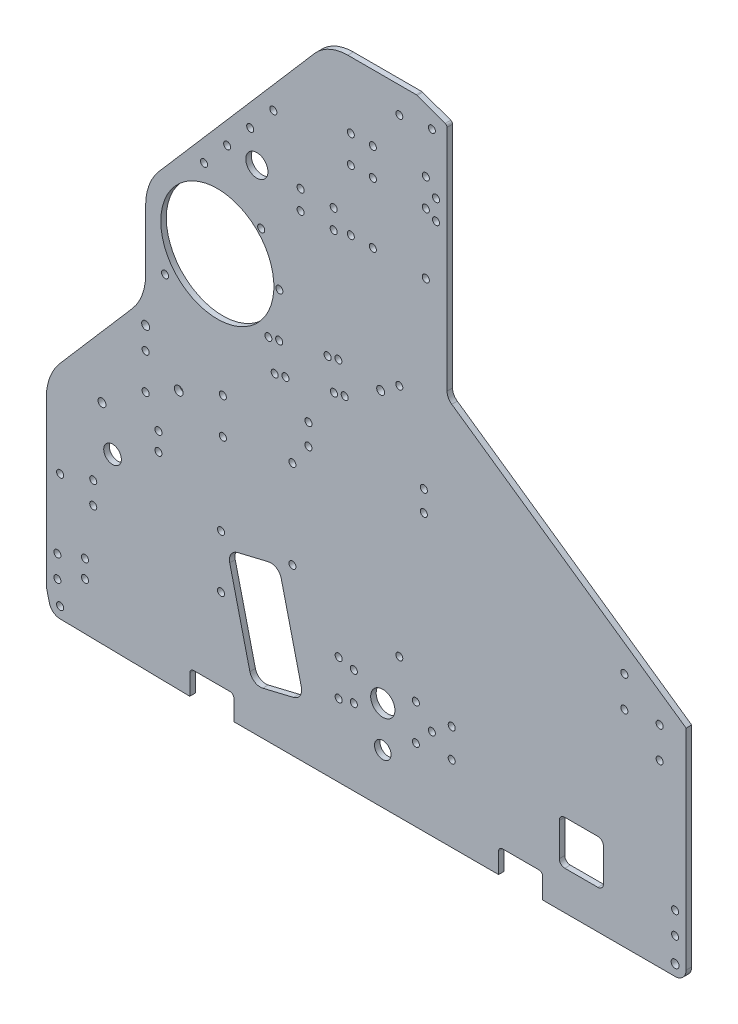
SolidWorks part; units mm, degrees
ref_plane "Front Plane" through (0, 0, 0) normal (0, 0, 1) x (1, 0, 0)
ref_plane "Top Plane" through (0, 0, 0) normal (0, 1, 0) x (1, 0, 0)
ref_plane "Right Plane" through (0, 0, 0) normal (1, 0, 0) x (0, 0, -1)
sketch "Sketch1" plane through (0, 0, 0) normal (0, 0, 1) x (1, 0, 0)
  line L0 (82.55, -20.32) -> (82.55, -6.35)
  line L2 (0, 0) -> (0, 157.48)
  line L4 (368.3, -20.32) -> (368.3, 106.68)
  line L5 (82.55, -6.35) -> (107.95, -6.35)
  line L6 (107.95, -6.35) -> (107.95, -20.32)
  line L7 (107.95, -20.32) -> (260.35, -20.32)
  line L8 (260.35, -20.32) -> (260.35, -6.35)
  line L9 (260.35, -6.35) -> (285.75, -6.35)
  line L10 (285.75, -6.35) -> (285.75, -20.32)
  line L11 (285.75, -20.32) -> (368.3, -20.32)
  line L12 (361.95, 12.7) -> (368.3, 12.7) construction
  line L13 (0, 0) -> (6.35, 0) construction
  line L14 (0.1896, -7.8901) -> (1.7771, -14.2401)
  line L15 (7.8295, -19.0491) -> (82.55, -20.32)
  line L16 (0, 0) -> (0, -6.35)
  line L17 (76.2, 128.905) -> (79.375, 128.905) construction
  line L18 (57.15, 118.5863) -> (101.6, 118.5862) construction
  line L19 (57.15, 118.5863) -> (57.15, 139.2238) construction
  line L20 (101.6, 118.5862) -> (101.6, 139.2237) construction
  line L21 (57.15, 139.2238) -> (101.6, 139.2237) construction
  line L22 (57.15, 118.5863) -> (101.6, 139.2237) construction
  line L23 (101.6, 118.5862) -> (57.15, 139.2238) construction
  line L25 (203.2, 59.805) -> (203.2, 194.805) construction
  line L26 (203.2, 194.805) -> (203.2, 329.805) construction
  line L27 (355.6, 332.105) -> (330.2, 332.105) construction
  line L28 (330.2, 332.105) -> (330.2, 217.805) construction
  line L29 (330.2, 217.805) -> (355.6, 217.805) construction
  line L30 (355.6, 217.805) -> (355.6, 332.105) construction
  line L31 (203.2, 344.805) -> (203.2, 194.805) construction
  line L32 (50.8, 332.105) -> (76.2, 332.105) construction
  line L33 (76.2, 332.105) -> (76.2, 217.805) construction
  line L34 (50.8, 217.805) -> (50.8, 332.105) construction
  line L35 (76.2, 217.805) -> (50.8, 217.805) construction
  line L36 (213.2, 344.805) -> (230.6638, 338.455)
  line L37 (203.2, 344.805) -> (161.925, 344.805)
  line L38 (203.2, 344.805) -> (213.2, 344.805)
  line L39 (348.5362, 344.805) -> (413.4623, 344.805)
  line L40 (348.5362, 344.805) -> (230.6638, 344.805) construction
  line L42 (161.925, 344.805) -> (0, 157.48)
  line L44 (230.6638, 338.455) -> (230.6638, 202.565)
  line L45 (230.6638, 202.565) -> (368.3, 106.68)
  line L46 (213.2, 344.805) -> (-141.0713, 344.805) construction
  circle A0 centre (6.35, 0) radius 2.032
  circle A1 centre (6.35, 12.7) radius 2.032
  circle A2 centre (361.95, 0) radius 2.032
  circle A3 centre (361.95, 12.7) radius 2.032
  arc A5 (1.7771, -14.2401) -> (7.8295, -19.0491) centre (7.9375, -12.7) ccw
  circle A6 centre (7.9375, -12.7) radius 2.032
  arc A7 (0, -6.35) -> (0.1896, -7.8901) centre (6.35, -6.35) ccw
  circle A8 centre (38.1, 78.105) radius 5.08
  circle A9 centre (76.2, 128.905) radius 2.54
  circle A10 centre (101.6, 118.5862) radius 2.032
  circle A11 centre (101.6, 139.2237) radius 2.032
  circle A12 centre (57.15, 139.2238) radius 2.032
  circle A13 centre (57.15, 118.5863) radius 2.032
  circle A15 centre (203.2, 59.805) radius 2
  circle A16 centre (203.2, 194.805) radius 2
  circle A17 centre (203.2, 329.805) radius 2
  circle A18 centre (63.5, 313.055) radius 2.032
  circle A20 centre (355.6, 332.105) radius 2.032
  circle A21 centre (330.2, 332.105) radius 2.032
  circle A22 centre (355.6, 217.805) radius 2.032
  circle A23 centre (330.2, 217.805) radius 2.032
  circle A24 centre (50.8, 332.105) radius 2.032
  circle A25 centre (76.2, 332.105) radius 2.032
  circle A26 centre (50.8, 217.805) radius 2.032
  circle A27 centre (76.2, 217.805) radius 2.032
  circle A28 centre (221.9319, 332.105) radius 2
  circle A29 centre (224.3138, 298.831) radius 2.032
  circle A30 centre (353.06, 100.7351) radius 2.032
  circle A31 centre (332.74, 115.9751) radius 2.032
  circle A32 centre (332.74, 98.1951) radius 2.032
  circle A33 centre (353.06, 82.9551) radius 2.032
  circle A34 centre (117.3562, 280.4276) radius 2.032
  circle A35 centre (104.0678, 265.0548) radius 2.032
  circle A36 centre (90.7795, 249.682) radius 2.032
  circle A38 centre (130.6445, 295.8004) radius 2.032
  circle A39 centre (68.326, 182.9237) radius 2.032
  circle A40 centre (224.3138, 287.401) radius 2.032
  point P82 (203.2, 344.805)
  point P83 (221.9319, 341.63)
  point P90 (368.3, 62.484)
  dimension "D6" = 4.064
  dimension "D10" = 6.35
  dimension "D11" = 4.064
  dimension "D17" = 38.1
  dimension "D27" = 4
  dimension "D31" = 4.064
  dimension "D32" = 41.275
  dimension "D36" = 4.064
  dimension "D47" = 39.624
  dimension "D48" = 4.064
  dimension "D25" = 5.08
  dimension "D26" = 4.064
  dimension "D52" = 4.064
  dimension "D65" = 4.064
  dimension "D69" = 10.16
  dimension "D2" = 127
  dimension "D3" = 13.97
  dimension "D4" = 25.4
  dimension "D5" = 152.4
  dimension "D7" = 12.7
  dimension "D8" = 6.35
  dimension "D9" = 20.32
  dimension "D12" = 12.7
  dimension "D13" = 1.5875
  dimension "D14" = 82.55
  dimension "D15" = 368.3
  dimension "D16" = 6.35
  dimension "D18" = 98.425
  dimension "D19" = 38.1
  dimension "D20" = 50.8
  dimension "D21" = 3.175
  dimension "D22" = 270
  dimension "D23" = 20.6375
  dimension "D24" = 44.45
  dimension "D28" = 135
  dimension "D29" = 12.7
  dimension "D30" = 15
  dimension "D33" = 63.5
  dimension "D34" = 27.4638
  dimension "D35" = 12.7
  dimension "D37" = 114.3
  dimension "D38" = 25.4
  dimension "D39" = 12.7
  dimension "D40" = 157.48
  dimension "D41" = 142.24
  dimension "D42" = 365.125
  dimension "D43" = 10
  dimension "D44" = 6.35
  dimension "D45" = 31.75
  dimension "D46" = 6.35
  dimension "D49" = 6.35
  dimension "D50" = 203.2
  dimension "D51" = 15.24
  dimension "D53" = 17.78
  dimension "D54" = 17.78
  dimension "D55" = 20.32
  dimension "D56" = 15.24
  dimension "D57" = 92.202
  dimension "D58" = 8.382
  dimension "D59" = 20.32
  dimension "D60" = 20.32
  dimension "D61" = 8.382
  dimension "D62" = 20.32
  dimension "D63" = 8.382
  dimension "D64" = 8.382
  dimension "D66" = 35.052
  dimension "D67" = 68.326
  dimension "D68" = 11.43
extrude "Boss-Extrude1" add sketch "Sketch1" along normal blind 3.175 contours L16 A7 L14 A5 L15 L2 A0 A1 A6 region at (171.4477, 119.565, 0)
fillet "Fillet1" radius 2.286 4 edges at (285.75, -6.35, 1.5875) (107.95, -6.35, 1.5875) (260.35, -6.35, 1.5875) (82.55, -6.35, 1.5875)
fillet "Fillet2" radius 6.35 1 edges at (230.6638, 202.565, 1.5875)
sketch "Sketch2" plane through (0, 0, 0) normal (0, 0, -1) x (-1, 0, 0)
  circle A0 centre (-100.5528, 71.086) radius 2.032 construction
  circle A1 centre (-100.5528, 40.606) radius 2.032 construction
  circle A2 centre (-22.225, 18.2025) radius 2.032 construction
  circle A3 centre (-22.225, 8.0425) radius 2.032 construction
  circle A4 centre (-100.5528, 71.086) radius 2.032
  circle A5 centre (-100.5528, 40.606) radius 2.032
  circle A6 centre (-22.225, 18.2025) radius 2.032
  circle A7 centre (-22.225, 8.0425) radius 2.032
extrude "Cut-Extrude1" cut sketch "Sketch2" against normal through all
fillet "Fillet3" radius 1.5875 2 edges at (230.6638, 338.455, 1.5875) (213.2, 344.805, 1.5875)
sketch "Sketch3" plane through (0, 0, 3.175) normal (0, 0, 1) x (1, 0, 0)
  line L0 (132.9524, 63.2646) -> (132.7215, 64.2281) construction
  line L1 (128.3814, 66.8897) -> (110.6828, 62.6472) construction
  line L2 (114.5132, 58.4237) -> (126.8822, 61.3887) construction
  line L3 (108.0212, 58.3071) -> (108.2522, 57.3436) construction
  line L4 (131.2006, 57.703) -> (140.0164, 20.9265) construction
  line L5 (144.0993, 16.7636) -> (132.9524, 63.2646) construction
  line L6 (108.2522, 57.3436) -> (119.3991, 10.8426) construction
  line L7 (121.1509, 16.4042) -> (112.3351, 53.1807) construction
  line L8 (119.3991, 10.8426) -> (119.6301, 9.8791) construction
  line L9 (144.3303, 15.8001) -> (144.0993, 16.7636) construction
  line L10 (137.8383, 15.6835) -> (125.4694, 12.7185) construction
  line L11 (123.9701, 7.2175) -> (141.6687, 11.4601) construction
  line L12 (132.9524, 63.2646) -> (132.7215, 64.2281)
  line L13 (128.3814, 66.8897) -> (110.6828, 62.6472)
  line L14 (114.5132, 58.4237) -> (126.8822, 61.3887)
  line L15 (108.0212, 58.3071) -> (108.2522, 57.3436)
  line L16 (131.2006, 57.703) -> (140.0164, 20.9265)
  line L17 (144.0993, 16.7636) -> (132.9524, 63.2646)
  line L18 (108.2522, 57.3436) -> (119.3991, 10.8426)
  line L19 (121.1509, 16.4042) -> (112.3351, 53.1807)
  line L20 (119.3991, 10.8426) -> (119.6301, 9.8791)
  line L21 (144.3303, 15.8001) -> (144.0993, 16.7636)
  line L22 (137.8383, 15.6835) -> (125.4694, 12.7185)
  line L23 (123.9701, 7.2175) -> (141.6687, 11.4601)
  line L24 (127.7894, 69.3598) -> (110.0908, 65.1172)
  line L25 (105.5512, 57.715) -> (105.7822, 56.7515)
  line L26 (105.7822, 56.7515) -> (116.9291, 10.2505)
  line L27 (116.9291, 10.2505) -> (117.16, 9.287)
  line L28 (124.5622, 4.7475) -> (142.2608, 8.99)
  line L29 (146.8003, 16.3922) -> (146.5694, 17.3557)
  line L30 (146.5694, 17.3557) -> (135.4225, 63.8567)
  line L31 (135.4225, 63.8567) -> (135.1915, 64.8202)
  line L32 (14.605, -0.1369) -> (103.7278, 32.3011) construction
  line L33 (14.605, -0.1369) -> (103.7278, 32.3011)
  line L34 (0, -6.35) -> (0, 157.48) construction
  line L35 (-39.6666, 74.7152) -> (103.7278, 126.9065) construction
  line L36 (26.9875, 46.9531) -> (26.9875, 59.6531) construction
  line L37 (107.95, -20.32) -> (260.35, -20.32) construction
  line L38 (64.5259, 92.5258) -> (64.5259, 102.9405) construction
  arc A0 (132.7215, 64.2281) -> (128.6308, 66.9403) centre (129.2206, 63.3889) ccw construction
  arc A1 (110.6828, 62.6472) -> (110.4377, 62.5791) centre (111.522, 59.1463) ccw construction
  arc A2 (128.6308, 66.9403) -> (128.3814, 66.8897) centre (129.2206, 63.3889) ccw construction
  arc A3 (110.4377, 62.5791) -> (108.0212, 58.3071) centre (111.522, 59.1463) ccw construction
  arc A4 (119.6301, 9.8791) -> (123.7207, 7.1669) centre (123.1309, 10.7183) ccw construction
  arc A5 (141.9139, 11.5281) -> (144.3303, 15.8001) centre (140.8295, 14.9609) ccw construction
  arc A6 (141.6687, 11.4601) -> (141.9139, 11.5281) centre (140.8295, 14.9609) ccw construction
  arc A7 (123.7207, 7.1669) -> (123.9701, 7.2175) centre (123.1309, 10.7183) ccw construction
  arc A8 (132.7215, 64.2281) -> (128.6308, 66.9403) centre (129.2206, 63.3889) ccw
  arc A9 (110.6828, 62.6472) -> (110.4377, 62.5791) centre (111.522, 59.1463) ccw
  arc A10 (128.6308, 66.9403) -> (128.3814, 66.8897) centre (129.2206, 63.3889) ccw
  arc A11 (110.4377, 62.5791) -> (108.0212, 58.3071) centre (111.522, 59.1463) ccw
  arc A12 (119.6301, 9.8791) -> (123.7207, 7.1669) centre (123.1309, 10.7183) ccw
  arc A13 (141.9139, 11.5281) -> (144.3303, 15.8001) centre (140.8295, 14.9609) ccw
  arc A14 (141.6687, 11.4601) -> (141.9139, 11.5281) centre (140.8295, 14.9609) ccw
  arc A15 (123.7207, 7.1669) -> (123.9701, 7.2175) centre (123.1309, 10.7183) ccw
  arc A16 (110.0908, 65.1172) -> (109.6726, 65.0012) centre (111.522, 59.1463) ccw
  arc A17 (109.6726, 65.0012) -> (105.5512, 57.715) centre (111.522, 59.1463) ccw
  arc A18 (117.16, 9.287) -> (124.1369, 4.6613) centre (123.1309, 10.7183) ccw
  arc A19 (124.1369, 4.6613) -> (124.5622, 4.7475) centre (123.1309, 10.7183) ccw
  arc A20 (142.2608, 8.99) -> (142.6789, 9.1061) centre (140.8295, 14.9609) ccw
  arc A21 (142.6789, 9.1061) -> (146.8003, 16.3922) centre (140.8295, 14.9609) ccw
  arc A22 (135.1915, 64.8202) -> (128.2147, 69.446) centre (129.2206, 63.3889) ccw
  arc A23 (128.2147, 69.446) -> (127.7894, 69.3598) centre (129.2206, 63.3889) ccw
  circle A26 centre (134.1438, 208.2281) radius 2.032 construction
  circle A33 centre (26.9875, 46.9531) radius 2.032
  circle A34 centre (26.9875, 59.6531) radius 2.032
  circle A35 centre (7.9375, 53.3031) radius 2.032
  circle A37 centre (32.0306, 100.8109) radius 31.75 construction
  circle A38 centre (32.0306, 100.8109) radius 2.286
  circle A39 centre (123.682, 233.4851) radius 2.032 construction
  circle A40 centre (64.5259, 102.9405) radius 2.032
  circle A41 centre (64.5259, 92.5258) radius 2.032
  circle A42 centre (134.1438, 208.2281) radius 2.032
  circle A43 centre (123.682, 233.4851) radius 2.032
  ellipse E0 centre (124.5974, 48.8487) end of major axis (128.5376, 61.3578) minor radius 6 (131.2006, 57.703) -> (126.8822, 61.3887) ccw construction
  ellipse E1 centre (122.2349, 48.2824) end of major axis (113.0518, 57.6456) minor radius 6 (114.5132, 58.4237) -> (112.3351, 53.1807) ccw construction
  ellipse E2 centre (127.7541, 25.2585) end of major axis (131.6942, 37.7675) minor radius 6 (121.1509, 16.4042) -> (125.4694, 12.7185) ccw construction
  ellipse E3 centre (130.1166, 25.8248) end of major axis (139.2998, 16.4616) minor radius 6 (137.8383, 15.6835) -> (140.0164, 20.9265) ccw construction
  ellipse E4 centre (124.5974, 48.8487) end of major axis (128.5376, 61.3578) minor radius 6 (131.2006, 57.703) -> (126.8822, 61.3887) ccw
  ellipse E5 centre (122.2349, 48.2824) end of major axis (131.4181, 38.9192) minor radius 6 (114.5132, 58.4237) -> (112.3351, 53.1807) ccw
  ellipse E6 centre (127.7541, 25.2585) end of major axis (123.8139, 12.7495) minor radius 6 (121.1509, 16.4042) -> (125.4694, 12.7185) ccw
  ellipse E7 centre (130.1166, 25.8248) end of major axis (139.2998, 16.4616) minor radius 6 (137.8383, 15.6835) -> (140.0164, 20.9265) ccw
  point P93 (26.9875, 53.3031)
  point P115 (32.0306, 100.8109)
  dimension "D3" = 63.5
  dimension "D4" = 4.572
  dimension "D8" = 4.064
  dimension "D2" = 88.9
  dimension "D5" = 7.9375
  dimension "D6" = 19.05
  dimension "D7" = 73.6231
  dimension "D9" = 12.7
  dimension "D10" = 10.4147
  dimension "D11" = 37.5384
  dimension "D12" = 45.5727
  dimension "D1" = 2.54
extrude "Cut-Extrude2" cut sketch "Sketch3" against normal through all contours A22 A23 L24 A16 A17 L25 L26 L27 A18 A19 L28 A20 A21 L29 L30 L31 A15 A12 L20 L18 L15 A11 A9 L13 A10 A8 L12 L17 L21 A13 A14 L23 | A12 A15 L23 A14 A13 L21 L17 L12 A8 A10 L13 A9 A11 L15 L18 L20 E7 L22 E6 L19 E5 L14 E4 L16 | L22 E7 L16 E4 L14 E5 L19 E6 | A38 | A41 | A40 | A35 | A34 | A33 | A43 | A42 region at (137.844, 39.8506, 3.175) region at (126.1758, 37.0536, 3.175) region at (128.1544, 68.6507, 3.175) region at (32.0306, 100.8109, 3.175) region at (64.5259, 102.9405, 3.175) region at (64.5259, 92.5258, 3.175)
sketch "Sketch4" plane through (0, 0, 3.175) normal (0, 0, 1) x (1, 0, 0)
  line L0 (57.15, 139.2238) -> (101.6, 139.2237) construction
  line L1 (168.275, 21.4312) -> (212.725, 21.4312) construction
  line L2 (168.275, 21.4312) -> (168.275, 42.0687) construction
  line L3 (168.275, 42.0687) -> (212.725, 42.0687) construction
  line L4 (212.725, 21.4312) -> (212.725, 42.0687) construction
  line L5 (168.275, 21.4312) -> (212.725, 42.0687) construction
  line L6 (168.275, 42.0687) -> (212.725, 21.4312) construction
  line L7 (57.15, 118.5863) -> (57.15, 139.2238) construction
  line L8 (107.95, -20.32) -> (260.35, -20.32) construction
  line L9 (193.675, 31.75) -> (177.005, 31.75) construction
  line L10 (190.5, 31.75) -> (193.675, 31.75) construction
  line L11 (6.35, 12.7) -> (361.95, 12.7) construction
  line L12 (107.95, -6.35) -> (107.95, -20.32) construction
  line L13 (193.675, 31.75) -> (220.6625, 31.75) construction
  line L14 (177.005, 23.4569) -> (177.005, 40.0431) construction
  line L15 (213.2, 44.805) -> (193.2, 44.805) construction
  line L16 (213.2, 44.805) -> (213.2, 344.805) construction
  line L17 (213.2, 344.805) -> (193.2, 344.805) construction
  line L18 (193.2, 44.805) -> (193.2, 344.805) construction
  line L19 (213.2, 44.805) -> (193.2, 344.805) construction
  line L20 (213.2, 344.805) -> (193.2, 44.805) construction
  line L21 (226.9319, 332.105) -> (226.9319, 31.75) construction
  line L22 (237.33, 40.0431) -> (233.3612, 40.0431) construction
  line L23 (237.33, 23.4569) -> (233.3612, 23.4569) construction
  circle A0 centre (168.275, 42.0687) radius 2.032
  circle A1 centre (212.725, 42.0687) radius 2.032
  circle A2 centre (212.725, 21.4312) radius 2.032
  circle A3 centre (168.275, 21.4312) radius 2.032
  circle A4 centre (193.675, 31.75) radius 6.985
  circle A7 centre (220.6625, 31.75) radius 14.2875 construction
  circle A8 centre (193.675, 31.75) radius 12.7 construction
  circle A9 centre (177.005, 40.0431) radius 2.032
  circle A10 centre (177.005, 23.4569) radius 2.032
  circle A11 centre (237.33, 40.0431) radius 2.032 construction
  circle A12 centre (237.33, 23.4569) radius 2.032 construction
  circle A13 centre (193.675, 8.4667) radius 4.7625
  circle A14 centre (221.9319, 31.75) radius 2.032
  circle A15 centre (221.9319, 31.75) radius 5 construction
  circle A16 centre (221.9319, 332.105) radius 5 construction
  circle A17 centre (233.3612, 23.4569) radius 2.032
  circle A18 centre (233.3612, 40.0431) radius 2.032
  point P0 (190.5, 31.75)
  point P26 (203.2, 194.805)
  point P38 (177.005, 31.75)
  dimension "D1" = 4.064
  dimension "D4" = 13.97
  dimension "D7" = 9.525
  dimension "D10" = 25.4
  dimension "D11" = 28.575
  dimension "D16" = 10
  dimension "D17" = 4.064
  dimension "D18" = 10
  dimension "D2" = 52.07
  dimension "D3" = 3.175
  dimension "D5" = 82.55
  dimension "D6" = 26.9875
  dimension "D8" = 20
  dimension "D9" = 300
  dimension "D12" = 16.67
  dimension "D13" = 16.5862
  dimension "D14" = 60.325
  dimension "D15" = 23.2833
  dimension "D19" = 3.9688
extrude "Cut-Extrude3" cut sketch "Sketch4" against normal through all
sketch "Sketch5" plane through (0, 0, 0) normal (0, 0, -1) x (-1, 0, 0)
  line L0 (-57.15, 223.5947) -> (-57.15, 165.3337)
  line L1 (-161.925, 344.805) -> (-52.7201, 218.4699) construction
  line L2 (-57.15, 165.3337) -> (0, 99.219)
  line L3 (0, -6.35) -> (0, 157.48) construction
  line L5 (-50.4199, 215.8089) -> (0, 157.48) construction
  line L6 (-57.15, 223.5947) -> (0, 157.48)
  line L7 (0, 157.48) -> (0, 99.219)
  line L8 (-361.95, -13.97) -> (-368.3, -13.97) construction
  line L9 (-361.95, -13.97) -> (-361.95, -20.32) construction
  line L10 (-285.75, -20.32) -> (-368.3, -20.32) construction
  line L11 (-368.3, -20.32) -> (-368.3, 106.68) construction
  circle A0 centre (-98.425, 208.2281) radius 32.5437
  circle A2 centre (-361.95, -13.97) radius 2.286
  dimension "D3" = 65.0875
  dimension "D7" = 4.572
  dimension "D1" = 38.1
  dimension "D2" = 57.15
  dimension "D4" = 41.275
  dimension "D5" = 41.275
  dimension "D6" = 6.35
extrude "Cut-Extrude5" cut sketch "Sketch5" against normal through all contours A0 | L7 L6 L0 L2 | A2 region at (28.575, 161.4068, 0) region at (98.425, 208.2281, 0)
fillet "Fillet4" radius 31.75 3 edges at (0, 99.219, 1.5875) (57.15, 165.3337, 1.5875) (57.15, 223.5947, 1.5875)
sketch "Sketch6" plane through (0, 0, 3.175) normal (0, 0, 1) x (1, 0, 0)
  line L0 (285.75, -20.32) -> (368.3, -20.32) construction
  line L1 (298.45, 27.305) -> (317.5, 27.305)
  line L2 (295.275, 24.13) -> (295.275, 5.08)
  line L3 (298.45, 1.905) -> (317.5, 1.905)
  line L4 (320.675, 24.13) -> (320.675, 5.08)
  line L5 (295.275, 27.305) -> (320.675, 1.905) construction
  line L6 (295.275, 1.905) -> (320.675, 27.305) construction
  line L7 (368.3, -20.32) -> (368.3, 106.68) construction
  arc A0 (295.275, 5.08) -> (298.45, 1.905) centre (298.45, 5.08) ccw
  arc A1 (317.5, 1.905) -> (320.675, 5.08) centre (317.5, 5.08) ccw
  arc A2 (317.5, 27.305) -> (320.675, 24.13) centre (317.5, 24.13) cw
  arc A3 (298.45, 27.305) -> (295.275, 24.13) centre (298.45, 24.13) ccw
  point P0 (307.975, 14.605)
  dimension "D2" = 3.175
  dimension "D1" = 25.4
  dimension "D3" = 22.225
  dimension "D4" = 47.625
extrude "Cut-Extrude6" cut sketch "Sketch6" against normal through all
fillet "Fillet5" radius 25.4 1 edges at (161.925, 344.805, 1.5875)
sketch "Sketch8" plane through (0, 0, 0) normal (0, 0, -1) x (-1, 0, 0)
  line L0 (-230.6638, 337.343) -> (-230.6638, 205.8802) construction
  line L1 (-230.6638, 255.905) -> (-175.26, 255.905) construction
  line L2 (-175.26, 255.905) -> (-175.26, 306.705) construction
  line L3 (-175.26, 306.705) -> (-230.6638, 306.705) construction
  line L4 (-173.5432, 344.805) -> (-212.9203, 344.805) construction
  line L7 (-107.95, -20.32) -> (-260.35, -20.32) construction
  circle A0 centre (-218.44, 290.83) radius 3.9687
  circle A1 centre (-218.44, 290.83) radius 2.032
  circle A2 centre (218.44, 265.7972) radius 3.9687
  circle A3 centre (218.44, 265.7972) radius 2.032
  circle A4 centre (-205.74, 290.83) radius 3.9687
  circle A5 centre (-205.74, 290.83) radius 2.032
  circle A6 centre (-187.96, 290.83) radius 3.9687
  circle A7 centre (-187.96, 290.83) radius 2.032
  circle A8 centre (-187.96, 306.705) radius 2.032
  circle A9 centre (-175.26, 290.83) radius 3.9687
  circle A10 centre (-175.26, 290.83) radius 2.032
  circle A11 centre (-205.74, 306.705) radius 2.032
  circle A13 centre (-205.74, 255.905) radius 2.032
  circle A14 centre (-187.96, 255.905) radius 2.032
  circle A16 centre (-218.44, 306.705) radius 2.032
  circle A17 centre (-175.26, 306.705) radius 2.032
  circle A18 centre (-175.26, 255.905) radius 2.032
  circle A19 centre (-218.44, 255.905) radius 2.032
  circle A20 centre (-218.44, 306.705) radius 3.9687
  circle A21 centre (-205.74, 306.705) radius 3.9687
  circle A22 centre (-175.26, 306.705) radius 3.9687
  circle A23 centre (-218.44, 255.905) radius 3.9687
  circle A24 centre (-205.74, 255.905) radius 3.9687
  circle A25 centre (-187.96, 255.905) radius 3.9687
  circle A26 centre (-175.26, 255.905) radius 3.9687
  circle A27 centre (-187.96, 306.705) radius 3.9687
  point P4 (-218.44, 265.7972)
  point P9 (-218.44, 265.4434)
  point P41 (-218.44, 262.262)
  point P42 (-204.0262, 265.7972)
  point P46 (-192.9925, 265.7972)
  point P50 (-175.26, 267.1388)
  point P51 (-218.44, 266.566)
  point P52 (-206.8871, 265.43)
  dimension "D1" = 7.9375
  dimension "D7" = 4.064
  dimension "D13" = 12.2237
  dimension "D2" = 12.2237
  dimension "D3" = 12.7
  dimension "D4" = 17.78
  dimension "D5" = 12.7
  dimension "D6" = 88.9
  dimension "D8" = 38.1
  dimension "D9" = 17.78
  dimension "D10" = 12.7
  dimension "D11" = 55.4037
  dimension "D12" = 12.7
  dimension "D14" = 311.15
extrude "Cut-Extrude7" cut sketch "Sketch8" against normal through all contours A16 | A17 | A18 | A19 | A8 | A14 | A1 | A7 | A10 region at (218.44, 306.705, 0) region at (175.26, 306.705, 0) region at (175.26, 255.905, 0) region at (218.44, 255.905, 0)
sketch "Sketch10" plane through (0, 0, 3.175) normal (0, 0, 1) x (1, 0, 0)
  circle A4 centre (141.6425, 74.6844) radius 2.032 construction
  circle A5 centre (141.6425, 125.4844) radius 2.032 construction
  circle A6 centre (141.6425, 74.6844) radius 2.032
  circle A7 centre (141.6425, 125.4844) radius 2.032
extrude "Cut-Extrude8" cut sketch "Sketch10" against normal through all
fillet "Fillet6" radius 6.35 1 edges at (368.3, -20.32, 1.5875)
sketch "Sketch11" plane through (0, 0, 3.175) normal (0, 0, 1) x (1, 0, 0)
  ellipse E4 centre (150.8814, 138.43) end of major axis (150.8814, 140.462) minor radius 2.032
  ellipse E5 centre (150.8814, 150.495) end of major axis (150.8814, 152.527) minor radius 2.032
  ellipse E6 centre (217.3024, 150.495) end of major axis (217.3024, 152.527) minor radius 2.032
  ellipse E7 centre (217.3024, 138.43) end of major axis (217.3024, 140.462) minor radius 2.032
extrude "Cut-Extrude9" cut sketch "Sketch11" against normal through all
sketch "Sketch12" plane through (0, 0, 0) normal (0, 0, -1) x (-1, 0, 0)
  line L0 (-173.5432, 344.805) -> (-212.9203, 344.805) construction
  circle A0 centre (-165.4175, 264.635) radius 2.032
  circle A1 centre (-203.2, 329.805) radius 2 construction
  circle A2 centre (-165.4175, 253.5225) radius 2.032
  circle A3 centre (-146.3675, 253.5225) radius 2.032
  circle A4 centre (-146.3675, 264.635) radius 2.032
  dimension "D1" = 80.17
  dimension "D2" = 4.064
  dimension "D3" = 37.7825
  dimension "D4" = 11.1125
  dimension "D5" = 19.05
extrude "Cut-Extrude10" cut sketch "Sketch12" against normal through all
sketch "Sketch14" plane through (0, 0, 0) normal (0, 0, -1) x (-1, 0, 0)
  line L0 (-130.6445, 295.8004) -> (-121.1847, 263.6885) construction
  line L1 (-121.1847, 263.6885) -> (-90.7795, 249.682) construction
  line L2 (-154.3272, 336.0154) -> (-64.88, 232.5373) construction
  line L4 (-118.517, 269.4796) -> (-115.3937, 261.0208) construction
  line L5 (-118.517, 269.4796) -> (-126.9758, 266.3562) construction
  line L6 (-126.9758, 266.3562) -> (-123.8524, 257.8974) construction
  line L7 (-115.3937, 261.0208) -> (-123.8524, 257.8974) construction
  line L8 (-118.517, 269.4796) -> (-123.8524, 257.8974) construction
  line L9 (-126.9758, 266.3562) -> (-115.3937, 261.0208) construction
  circle A0 centre (-121.1847, 263.6885) radius 6.376
  dimension "D1" = 22.225
  dimension "D2" = 9.017
extrude "Cut-Extrude11" cut sketch "Sketch14" against normal through all
sketch "Sketch15" plane through (0, 0, 3.175) normal (0, 0, 1) x (1, 0, 0)
  line L1 (27.1508, 77.7471) -> (81.7263, 77.7471) construction
  line L2 (57.15, 139.2238) -> (57.15, 151.9238) construction
  line L3 (27.1508, 77.7471) -> (52.3291, 153.5255) construction
  line L4 (56.0505, 156.8833) -> (192.439, 187.1199) construction
  circle A0 centre (27.1508, 77.7471) radius 2.159 construction
  circle A1 centre (27.1508, 77.7471) radius 2.159 construction
  circle A2 centre (57.15, 139.2238) radius 2.032 construction
  circle A3 centre (57.15, 139.2238) radius 2.032 construction
  circle A4 centre (57.15, 151.9238) radius 2.286
  circle A5 centre (192.439, 187.1199) radius 2.286
  circle A6 centre (57.15, 151.9238) radius 5.08 construction
  arc A9 (163.8737, 173.6806) -> (164.5125, 170.7993) centre (165.557, 172.5423) ccw construction
  arc A10 (173.4398, 172.7784) -> (172.801, 175.6597) centre (171.7565, 173.9167) ccw construction
  arc A11 (172.801, 175.6597) -> (173.4398, 172.7784) centre (171.7565, 173.9167) ccw construction
  arc A12 (164.5125, 170.7993) -> (163.8737, 173.6806) centre (165.557, 172.5423) ccw construction
  arc A13 (169.1589, 192.0883) -> (169.7976, 189.2071) centre (168.1143, 190.3453) ccw construction
  arc A14 (169.7976, 189.2071) -> (169.1589, 192.0883) centre (168.1143, 190.3453) ccw construction
  arc A15 (160.2316, 190.1092) -> (160.8704, 187.2279) centre (161.9149, 188.9709) ccw construction
  arc A16 (160.8704, 187.2279) -> (160.2316, 190.1092) centre (161.9149, 188.9709) ccw construction
  arc A17 (129.7766, 166.1214) -> (130.4154, 163.2402) centre (131.4599, 164.9832) ccw construction
  arc A18 (139.3426, 165.2193) -> (138.7039, 168.1005) centre (137.6593, 166.3576) ccw construction
  arc A19 (138.7039, 168.1005) -> (139.3426, 165.2193) centre (137.6593, 166.3576) ccw construction
  arc A20 (130.4154, 163.2402) -> (129.7766, 166.1214) centre (131.4599, 164.9832) ccw construction
  arc A21 (135.7005, 181.6479) -> (135.0617, 184.5292) centre (134.0172, 182.7862) ccw construction
  arc A22 (135.0617, 184.5292) -> (135.7005, 181.6479) centre (134.0172, 182.7862) ccw construction
  arc A23 (126.1345, 182.55) -> (126.7732, 179.6688) centre (127.8177, 181.4118) ccw construction
  arc A24 (126.7732, 179.6688) -> (126.1345, 182.55) centre (127.8177, 181.4118) ccw construction
  arc A25 (163.8737, 173.6806) -> (164.5125, 170.7993) centre (165.557, 172.5423) ccw
  arc A26 (173.4398, 172.7784) -> (172.801, 175.6597) centre (171.7565, 173.9167) ccw
  arc A27 (172.801, 175.6597) -> (173.4398, 172.7784) centre (171.7565, 173.9167) ccw
  arc A28 (164.5125, 170.7993) -> (163.8737, 173.6806) centre (165.557, 172.5423) ccw
  arc A29 (169.1589, 192.0883) -> (169.7976, 189.2071) centre (168.1143, 190.3453) ccw
  arc A30 (169.7976, 189.2071) -> (169.1589, 192.0883) centre (168.1143, 190.3453) ccw
  arc A31 (160.2316, 190.1092) -> (160.8704, 187.2279) centre (161.9149, 188.9709) ccw
  arc A32 (160.8704, 187.2279) -> (160.2316, 190.1092) centre (161.9149, 188.9709) ccw
  arc A33 (129.7766, 166.1214) -> (130.4154, 163.2402) centre (131.4599, 164.9832) ccw
  arc A34 (139.3426, 165.2193) -> (138.7039, 168.1005) centre (137.6593, 166.3576) ccw
  arc A35 (138.7039, 168.1005) -> (139.3426, 165.2193) centre (137.6593, 166.3576) ccw
  arc A36 (130.4154, 163.2402) -> (129.7766, 166.1214) centre (131.4599, 164.9832) ccw
  arc A37 (135.7005, 181.6479) -> (135.0617, 184.5292) centre (134.0172, 182.7862) ccw
  arc A38 (135.0617, 184.5292) -> (135.7005, 181.6479) centre (134.0172, 182.7862) ccw
  arc A39 (126.1345, 182.55) -> (126.7732, 179.6688) centre (127.8177, 181.4118) ccw
  arc A40 (126.7732, 179.6688) -> (126.1345, 182.55) centre (127.8177, 181.4118) ccw
  dimension "D2" = 4.572
  dimension "D6" = 10.16
  dimension "D1" = 12.7
  dimension "D3" = 139.7
  dimension "D4" = 12.5
extrude "Cut-Extrude12" cut sketch "Sketch15" against normal through all
